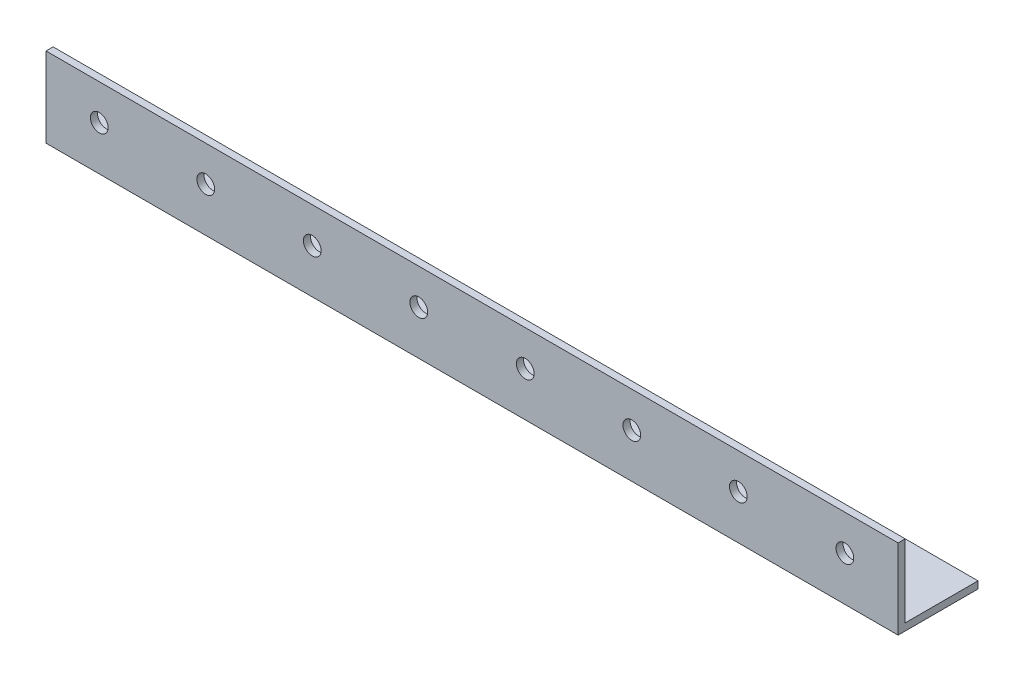
SolidWorks part; units mm, degrees
ref_plane "Спереди" through (0, 0, 0) normal (0, 0, 1) x (1, 0, 0)
ref_plane "Сверху" through (0, 0, 0) normal (0, 1, 0) x (1, 0, 0)
ref_plane "Справа" through (0, 0, 0) normal (1, 0, 0) x (0, 0, -1)
sketch "Эскиз1" plane through (0, 0, 0) normal (1, 0, 0) x (0, 0, -1)
  line L0 (0, 0) -> (0, 45)
  line L1 (0, 0) -> (45, 0)
  dimension "D1" = 45
  dimension "D2" = 45
extrude "Вытянуть-Тонкостенный1" add sketch "Эскиз1" along normal blind 480 thin thin type one direction reverse wall 4
sketch "Эскиз2" plane through (0, 0, 0) normal (0, 0, 1) x (1, 0, 0)
  circle A0 centre (30, 25) radius 5
  circle A1 centre (90, 25) radius 5
  circle A2 centre (150, 25) radius 5
  circle A3 centre (210, 25) radius 5
  circle A8 centre (270, 25) radius 5
  circle A29 centre (330, 25) radius 5
  circle A30 centre (390, 25) radius 5
  circle A31 centre (450, 25) radius 5
  dimension "D1" = 8
extrude "Вырез-Вытянуть1" cut sketch "Эскиз2" against normal through all
